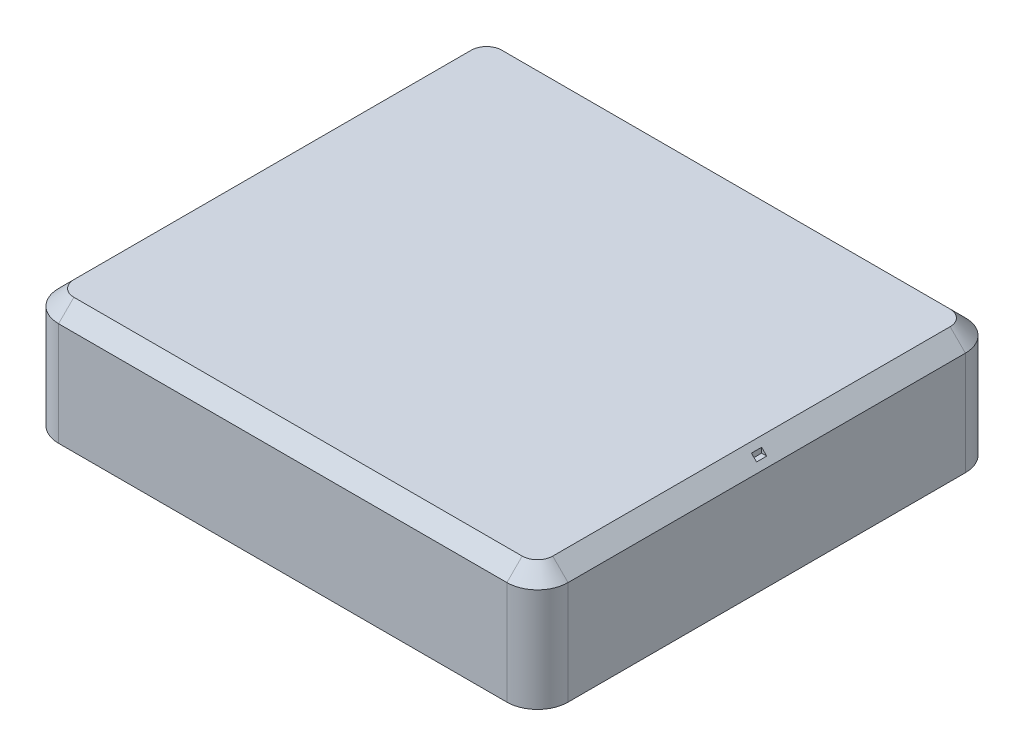
SolidWorks part; units mm, degrees
ref_plane "Front Plane" through (0, 0, 0) normal (0, 0, 1) x (1, 0, 0)
ref_plane "Top Plane" through (0, 0, 0) normal (0, 1, 0) x (1, 0, 0)
ref_plane "Right Plane" through (0, 0, 0) normal (1, 0, 0) x (0, 0, -1)
sketch "Sketch1" plane through (0, 0, 0) normal (0, 0, 1) x (1, 0, 0)
  line L1 (0, 0) -> (50, 0)
  line L2 (0, 0) -> (0, 11.6667)
  line L3 (0, 11.6667) -> (50, 11.6667)
  line L4 (50, 0) -> (50, 11.6667)
  dimension "D1" = 11.6667
  dimension "D2" = 50
extrude "Boss-Extrude1" add sketch "Sketch1" along normal blind 45
sketch "Sketch2" plane through (50, 0, 0) normal (1, 0, 0) x (0, 0, -1)
  line L5 (-45, 11.6667) -> (0, 11.6667) construction
  line L6 (-23, 11.6667) -> (-22, 11.6667)
  line L7 (-23, 11.6667) -> (-23, 10.6667)
  line L8 (-23, 10.6667) -> (-22, 10.6667)
  line L9 (-22, 11.6667) -> (-22, 10.6667)
  line L10 (-45, 0) -> (-45, 11.6667) construction
  dimension "D1" = 1
  dimension "D2" = 1
  dimension "D3" = 22
extrude "Cut-Extrude1" cut sketch "Sketch2" against normal blind 1
shell "Shell1" thickness 2.5 removed face at (25, 0, 22.5)
sketch "Sketch3" plane through (0, 0, 0) normal (0, -1, 0) x (1, 0, 0)
  line L0 (2.5, 42.5) -> (2.5, 2.5) construction
  line L1 (1.3, 43.7) -> (48.7, 43.7)
  line L2 (1.3, 43.7) -> (1.3, 1.3)
  line L3 (1.3, 1.3) -> (48.7, 1.3)
  line L4 (48.7, 43.7) -> (48.7, 1.3)
  line L5 (47.5, 42.5) -> (2.5, 42.5) construction
  line L6 (47.5, 42.5) -> (47.5, 2.5) construction
  line L7 (47.5, 2.5) -> (2.5, 2.5) construction
  line L13 (2.5, 42.5) -> (47.5, 42.5)
  line L14 (2.5, 42.5) -> (2.5, 2.5)
  line L15 (2.5, 2.5) -> (47.5, 2.5)
  line L16 (47.5, 42.5) -> (47.5, 2.5)
  dimension "D1" = 1.2
  dimension "D2" = 1.2
  dimension "D3" = 1.2
  dimension "D4" = 1.2
extrude "Cut-Extrude3" cut sketch "Sketch3" against normal blind 2.5
fillet "Fillet1" radius 1 4 edges at (1.3, 1.25, 1.3) (48.7, 1.25, 1.3) (48.7, 1.25, 43.7) (1.3, 1.25, 43.7)
fillet "Fillet2" radius 3 4 edges at (0, 5.8333, 0) (50, 5.8333, 0) (0, 5.8333, 45) (50, 5.8333, 45)
chamfer "Chamfer1" distance 1.5 angle 45 8 edges at (50, 11.6667, 32.5) (49.1213, 11.6667, 44.1213) (49.1213, 11.6667, 0.8787) (25, 11.6667, 45) (25, 11.6667, 0) (0.8787, 11.6667, 44.1213) (0.8787, 11.6667, 0.8787) (0, 11.6667, 22.5)
